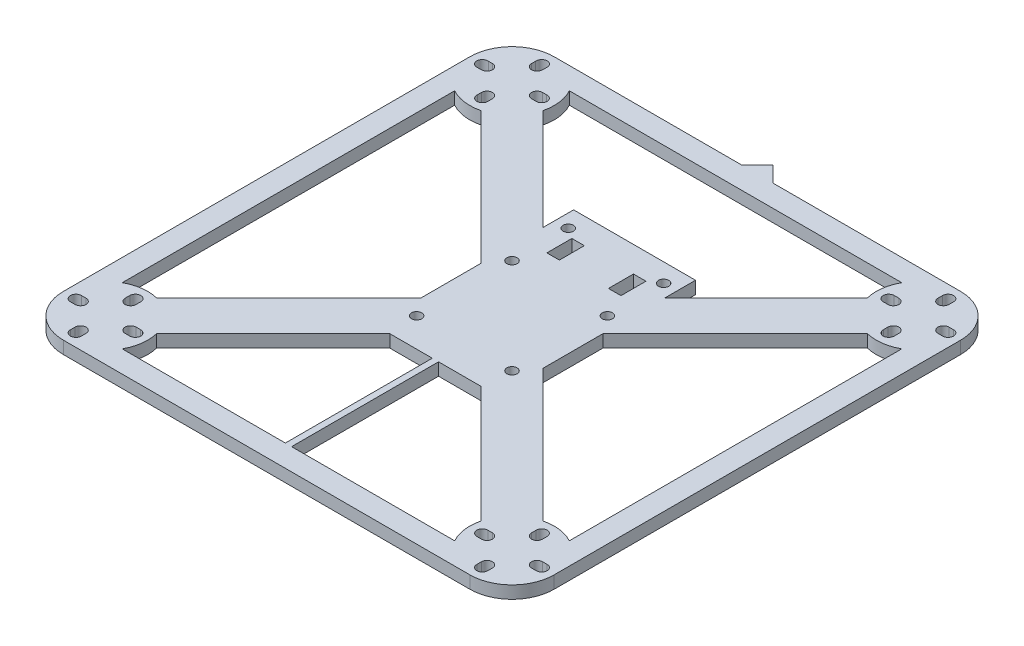
SolidWorks part; units mm, degrees
ref_plane "Front Plane" through (0, 0, 0) normal (0, 0, 1) x (1, 0, 0)
ref_plane "Top Plane" through (0, 0, 0) normal (0, 1, 0) x (1, 0, 0)
ref_plane "Right Plane" through (0, 0, 0) normal (1, 0, 0) x (0, 0, -1)
sketch "Sketch1" plane through (0, 0, 0) normal (0, 1, 0) x (1, 0, 0)
  line L0 (0, 78.5) -> (0, -78.5) construction
  line L1 (-78.5, 78.5) -> (78.5, 78.5)
  line L2 (-78.5, 78.5) -> (-78.5, -78.5)
  line L3 (-78.5, -78.5) -> (78.5, -78.5)
  line L4 (78.5, 78.5) -> (78.5, -78.5)
  line L5 (-78.5, 78.5) -> (78.5, -78.5) construction
  line L6 (-78.5, -78.5) -> (78.5, 78.5) construction
  line L7 (78.5, 0) -> (-78.5, 0) construction
  line L8 (-1, 65) -> (-1, 0) construction
  line L9 (-83.4497, 73.5503) -> (73.5503, -83.4497)
  line L10 (-73.5503, 83.4497) -> (83.4497, -73.5503)
  line L11 (-73.5503, -83.4497) -> (83.4497, 73.5503)
  line L12 (-83.4497, -73.5503) -> (73.5503, 83.4497)
  line L13 (-53.1678, 71.5) -> (53.1678, 71.5)
  line L14 (-53.1678, -71.5) -> (53.1678, -71.5)
  line L15 (71.5, -53.1678) -> (71.5, 53.1678)
  line L16 (-71.5, -53.1678) -> (-71.5, 53.1678)
  circle A0 centre (-65, 65) radius 13.5
  circle A1 centre (-65, 65) radius 64
  circle A2 centre (65, 65) radius 13.5
  circle A3 centre (-65, -65) radius 13.5
  circle A4 centre (65, -65) radius 13.5
  point P0 (0, 0)
  dimension "D1" = 27
  dimension "D2" = 128
  dimension "D3" = 2
  dimension "D4" = 14
  dimension "D5" = 7
extrude "Base shape" add sketch "Sketch1" along normal blind 4 contours L12 A3 L11 L9 | A4 L10 L11 L9 | L11 A2 L12 L10 | L9 A1 L10 A0 | A1 L9 L12 L10 | L12 L9 L11 L10 | L13 A1 L1 A0 | L13 A2 L1 A1 | A4 L4 A2 L15 | A4 L14 A3 L3 | L2 A3 L16 A1 | L2 A1 L16 A0 | A0 | A2 | A4 | A3 region at (-29.268, 0, -75.0845) region at (-75.0845, 0, -29.268) region at (27.4447, 0, -75.1014) region at (-37.8705, 0, -37.8705) region at (-75.1014, 0, 27.4447) region at (-12.3929, 0, -12.3929) region at (30.427, 0, -30.427) region at (0, 0, 0) region at (-30.427, 0, 30.427) region at (30.427, 0, 30.427) region at (75.0932, 0, 0) region at (0, 0, 75.0932)
sketch "Sketch2" plane through (0, 4, 0) normal (0, 1, 0) x (1, 0, 0)
  line L0 (-65, 74.5) -> (-65, 55.5) construction
  line L1 (-74.5, 65) -> (-55.5, 65) construction
  line L2 (0, 78.5) -> (0, -78.5) construction
  line L3 (-65, 78.5) -> (65, 78.5) construction
  line L4 (-65, -78.5) -> (65, -78.5) construction
  line L5 (-78.5, 0) -> (78.5, 0) construction
  line L6 (-78.5, 65) -> (-78.5, -65) construction
  line L7 (78.5, 65) -> (78.5, -65) construction
  line L8 (-66.75, 74.5) -> (-66.75, 73)
  line L9 (-63.25, 74.5) -> (-63.25, 73)
  line L10 (-74.5, 66.75) -> (-73, 66.75)
  line L11 (-74.5, 63.25) -> (-73, 63.25)
  line L12 (-66.75, 57) -> (-66.75, 55.5)
  line L13 (-63.25, 57) -> (-63.25, 55.5)
  line L14 (-57, 66.75) -> (-55.5, 66.75)
  line L15 (-57, 63.25) -> (-55.5, 63.25)
  line L16 (63.25, 57) -> (63.25, 55.5)
  line L17 (66.75, 57) -> (66.75, 55.5)
  line L18 (74.5, 63.25) -> (73, 63.25)
  line L19 (74.5, 66.75) -> (73, 66.75)
  line L20 (63.25, 74.5) -> (63.25, 73)
  line L21 (66.75, 74.5) -> (66.75, 73)
  line L22 (57, 66.75) -> (55.5, 66.75)
  line L23 (57, 63.25) -> (55.5, 63.25)
  line L24 (-66.75, -57) -> (-66.75, -55.5)
  line L25 (-63.25, -57) -> (-63.25, -55.5)
  line L26 (-57, -63.25) -> (-55.5, -63.25)
  line L27 (-57, -66.75) -> (-55.5, -66.75)
  line L28 (-74.5, -63.25) -> (-73, -63.25)
  line L29 (-74.5, -66.75) -> (-73, -66.75)
  line L30 (-63.25, -74.5) -> (-63.25, -73)
  line L31 (-66.75, -74.5) -> (-66.75, -73)
  line L32 (57, -63.25) -> (55.5, -63.25)
  line L33 (57, -66.75) -> (55.5, -66.75)
  line L34 (66.75, -74.5) -> (66.75, -73)
  line L35 (63.25, -74.5) -> (63.25, -73)
  line L36 (74.5, -66.75) -> (73, -66.75)
  line L37 (74.5, -63.25) -> (73, -63.25)
  line L38 (66.75, -57) -> (66.75, -55.5)
  line L39 (63.25, -57) -> (63.25, -55.5)
  circle A0 centre (-65, 65) radius 9.5
  circle A1 centre (-65, 65) radius 8
  circle A2 centre (-65, 74.5) radius 1.75
  circle A3 centre (-65, 55.5) radius 1.75
  circle A4 centre (-57, 65) radius 1.75
  circle A5 centre (-73, 65) radius 1.75
  circle A6 centre (-65, 73) radius 1.75
  circle A7 centre (-55.5, 65) radius 1.75
  circle A8 centre (-74.5, 65) radius 1.75
  circle A9 centre (-65, 57) radius 1.75
  circle A10 centre (65, 57) radius 1.75
  circle A11 centre (65, 55.5) radius 1.75
  circle A12 centre (73, 65) radius 1.75
  circle A13 centre (74.5, 65) radius 1.75
  circle A14 centre (65, 73) radius 1.75
  circle A15 centre (65, 74.5) radius 1.75
  circle A16 centre (57, 65) radius 1.75
  circle A17 centre (55.5, 65) radius 1.75
  circle A18 centre (-65, -57) radius 1.75
  circle A19 centre (-65, -55.5) radius 1.75
  circle A20 centre (-57, -65) radius 1.75
  circle A21 centre (-55.5, -65) radius 1.75
  circle A22 centre (-74.5, -65) radius 1.75
  circle A23 centre (-73, -65) radius 1.75
  circle A24 centre (-65, -74.5) radius 1.75
  circle A25 centre (-65, -73) radius 1.75
  circle A26 centre (55.5, -65) radius 1.75
  circle A27 centre (57, -65) radius 1.75
  circle A28 centre (65, -74.5) radius 1.75
  circle A29 centre (65, -73) radius 1.75
  circle A30 centre (74.5, -65) radius 1.75
  circle A31 centre (73, -65) radius 1.75
  circle A32 centre (65, -55.5) radius 1.75
  circle A33 centre (65, -57) radius 1.75
  dimension "D1" = 19
  dimension "D2" = 16
  dimension "D3" = 3.5
extrude "Motor mounting holes" cut sketch "Sketch2" against normal up to next contours A27 A26 | A26 A27 | A27 A26 | A27 L32 A26 | A27 A26 L33 | A29 A28 | A28 A29 | A28 A29 | A29 L35 A28 | A29 A28 L34 | A31 A30 | A30 A31 | A31 A30 | A31 A30 L37 | A31 L36 A30 | A33 A32 | A32 A33 | A33 A32 | A33 A32 L39 | A33 L38 A32 | A17 A16 | A17 A16 | A16 A17 | L22 A17 A16 | A16 A17 L23 | A11 A10 | A11 A10 | A10 A11 | L16 A11 A10 | A10 A11 L17 | A12 A13 | A13 A12 | A13 A12 | A12 A13 L19 | L18 A13 A12 | A14 A15 | A15 A14 | A15 A14 | A14 A15 L20 | L21 A15 A14 | A8 A5 L10 A0 | A8 A0 L11 A5 | A6 A2 A0 L8 | A6 L9 A0 A2 | A7 A4 L15 A0 | A7 A0 L14 A4 | A9 L12 A0 A3 | A9 A3 A0 L13 | A19 A18 | A19 A18 | A18 A19 | A18 A19 L24 | L25 A19 A18 | A22 A23 | A23 A22 | A23 A22 | A22 A23 L28 | L29 A23 A22 | A21 A20 | A21 A20 | A20 A21 | A20 A21 L26 | L27 A21 A20 | A24 A25 | A25 A24 | A25 A24 | A24 A25 L31 | L30 A25 A24 | A8 | A5 | A2 | A6 | A4 | A7 | A9 | A3 region at (-66.6996, 4, -73.7469) region at (-73.7469, 4, -66.6996) region at (-63.3004, 4, -73.7469) region at (-56.2531, 4, -66.6996) region at (-73.7469, 4, -63.3004) region at (-66.6996, 4, -56.2531) region at (-56.2531, 4, -63.3004) region at (-63.3004, 4, -56.2531) region at (63.3002, 4, -56.25) region at (65, 4, -57.6692) region at (65, 4, -54.8308) region at (66.6998, 4, -56.25) region at (65, 4, -56.25) region at (75.1692, 4, -65) region at (73.75, 4, -63.3002) region at (72.3308, 4, -65) region at (73.75, 4, -65) region at (73.75, 4, -66.6998) region at (63.3002, 4, -73.75) region at (65, 4, -75.1692) region at (65, 4, -72.3308) region at (66.6998, 4, -73.75) region at (65, 4, -73.75) region at (56.25, 4, -66.6998) region at (57.6692, 4, -65) region at (54.8308, 4, -65) region at (56.25, 4, -65) region at (56.25, 4, -63.3002) region at (-65, 4, 57.6692) region at (-66.6998, 4, 56.25) region at (-65, 4, 54.8308) region at (-63.3002, 4, 56.25) region at (-65, 4, 56.25) region at (-57.6692, 4, 65) region at (-56.25, 4, 63.3002) region at (-54.8308, 4, 65) region at (-56.25, 4, 66.6998) region at (-56.25, 4, 65) region at (-75.1692, 4, 65) region at (-73.75, 4, 63.3002) region at (-72.3308, 4, 65) region at (-73.75, 4, 66.6998) region at (-73.75, 4, 65) region at (-63.3002, 4, 73.75) region at (-65, 4, 75.1692) region at (-65, 4, 72.3308) region at (-66.6998, 4, 73.75) region at (-65, 4, 73.75) region at (56.25, 4, 63.3002) region at (57.6692, 4, 65) region at (54.8308, 4, 65) region at (56.25, 4, 65) region at (56.25, 4, 66.6998) region at (66.6998, 4, 73.75) region at (65, 4, 75.1692) region at (65, 4, 72.3308) region at (63.3002, 4, 73.75) region at (65, 4, 73.75) region at (75.1692, 4, 65) region at (73.75, 4, 66.6998)
sketch "Sketch3" plane through (0, 0, 0) normal (0, -1, 0) x (1, 0, 0)
  line L0 (0, -71.5) -> (0, -83.5) construction
  line L1 (-53.1678, -71.5) -> (53.1678, -71.5) construction
  line L2 (-65, -78.5) -> (65, -78.5) construction
  line L3 (0, -83.5) -> (-5, -78.5)
  line L4 (-5, -78.5) -> (5, -78.5)
  line L5 (0, -83.5) -> (5, -78.5)
  point P10 (0, -78.5)
  dimension "D1" = 5
  dimension "D2" = 45
extrude "Forward arrow" add sketch "Sketch3" against normal up to surface (4 mm away) contours L4 L0 L5 | L0 L4 L3 region at (1.6667, 0, -80.1667) region at (-1.6667, 0, -80.1667) up to face at (65, 4, 73.75)
sketch "Sketch5" plane through (0, 0, 0) normal (0, -1, 0) x (1, 0, 0)
  line L1 (18, 23) -> (-18, 23) construction
  line L2 (0, 23) -> (0, 24.5) construction
  line L3 (19.5, -24.5) -> (-19.5, -24.5)
  line L4 (18, 0) -> (19.5, 0) construction
  line L5 (18, -23) -> (18, 23) construction
  line L6 (7.85, -39.2) -> (-4.95, -39.2) construction
  line L12 (19.5, -24.5) -> (19.5, 24.5)
  line L13 (19.5, 24.5) -> (-19.5, 24.5)
  line L14 (-19.5, -24.5) -> (-19.5, 24.5)
  line L15 (19.5, -24.5) -> (-19.5, 24.5) construction
  line L16 (19.5, 24.5) -> (-19.5, -24.5) construction
  line L17 (-19.5, -24.5) -> (19.5, -24.5)
  line L18 (-19.5, -24.5) -> (-19.5, -39.2)
  line L19 (-19.5, -39.2) -> (19.5, -39.2)
  line L20 (19.5, -24.5) -> (19.5, -39.2)
  point P6 (0, 0)
  dimension "D1" = 1.5
extrude "OSD cover" add sketch "Sketch5" against normal up to surface (4 mm away) contours L20 L3 L18 L19 | L14 L3 L12 L13 region at (0, 0, -31.85) region at (0, 0, 0) up to face at (65, 4, 73.75)
sketch "Sketch7" plane through (0, 4, 0) normal (0, 1, 0) x (1, 0, 0)
  line L0 (18, 23) -> (-18, 23) construction
  line L1 (-7.85, 23) -> (-11.85, 23)
  line L2 (-7.85, 23) -> (-7.85, 31)
  line L3 (-7.85, 31) -> (-11.85, 31)
  line L4 (-11.85, 23) -> (-11.85, 31)
  line L5 (-7.85, 39.2) -> (-7.85, 23) construction
  line L6 (0, -24.5) -> (0, 39.2) construction
  line L9 (14.6005, -24.5) -> (-14.6005, -24.5) construction
  line L10 (7.85, 39.2) -> (-4.95, 39.2) construction
  line L11 (7.85, 31) -> (11.85, 31)
  line L12 (11.85, 23) -> (11.85, 31)
  line L13 (7.85, 23) -> (11.85, 23)
  line L14 (7.85, 23) -> (7.85, 31)
  circle A0 centre (-15.25, -15.25) radius 1.65 construction
  circle A1 centre (-15.25, 15.25) radius 1.65 construction
  circle A2 centre (-15.25, 33.25) radius 1.65 construction
  circle A3 centre (15.25, 33.25) radius 1.65 construction
  circle A4 centre (15.25, 15.25) radius 1.65 construction
  circle A5 centre (15.25, -15.25) radius 1.65 construction
  circle A6 centre (-15.25, -15.25) radius 1.65
  circle A7 centre (-15.25, 15.25) radius 1.65
  circle A8 centre (-15.25, 33.25) radius 1.65
  circle A9 centre (15.25, 33.25) radius 1.65
  circle A10 centre (15.25, 15.25) radius 1.65
  circle A11 centre (15.25, -15.25) radius 1.65
  dimension "D2" = 8
  dimension "D1" = 4
extrude "Main holes" cut sketch "Sketch7" against normal up to next contours A11 | A10 | A9 | A8 | A7 | A6 | L3 L4 L1 L2 | L11 L12 L13 L14
sketch "Sketch8" plane through (0, 0, 0) normal (0, -1, 0) x (1, 0, 0)
  line L0 (0, 78.5) -> (0, -71.5) construction
  line L1 (-65, 78.5) -> (65, 78.5) construction
  line L2 (-53.1678, -71.5) -> (53.1678, -71.5) construction
  line L3 (14.6005, 24.5) -> (-14.6005, 24.5) construction
  line L4 (-1, 24.5) -> (1, 24.5)
  line L5 (-1, 24.5) -> (-1, 71.5)
  line L6 (-1, 71.5) -> (1, 71.5)
  line L7 (1, 24.5) -> (1, 71.5)
  line L8 (-53.1678, 71.5) -> (53.1678, 71.5) construction
  line L9 (0, 71.5) -> (0, 24.5) construction
  dimension "D1" = 2
extrude "VTX wire support" add sketch "Sketch8" against normal up to surface (4 mm away) up to face at (-9.85, 4, -27)
equation "\"MotorDiameter\"=27"
equation "\"D1@Sketch1\"=\"MotorDiameter\""
equation "\"PropDiameter\"=128"
equation "\"D2@Sketch1\"=\"PropDiameter\""
equation "\"PropDistance\"=2"
equation "\"D3@Sketch1\"=\"PropDistance\""
equation "\"ArmWidth\"=14"
equation "\"D4@Sketch1\"=\"ArmWidth\""
equation "\"FrameDepth\"=4"
equation "\"D1@Base shape\" = \"FrameDepth\""
equation "\"D5@Sketch1\"=\"ArmWidth\"/2"
equation "\"MotorHoleOuterDiameter\"=19"
equation "\"D1@Sketch2\"=\"MotorHoleOuterDiameter\""
equation "\"MotorHoleInnerDiameter\"=16"
equation "\"D2@Sketch2\"=\"MotorHoleInnerDiameter\""
equation "\"MotorHoleDiameter\"=3.5"
equation "\"D3@Sketch2\"=\"MotorHoleDiameter\""
